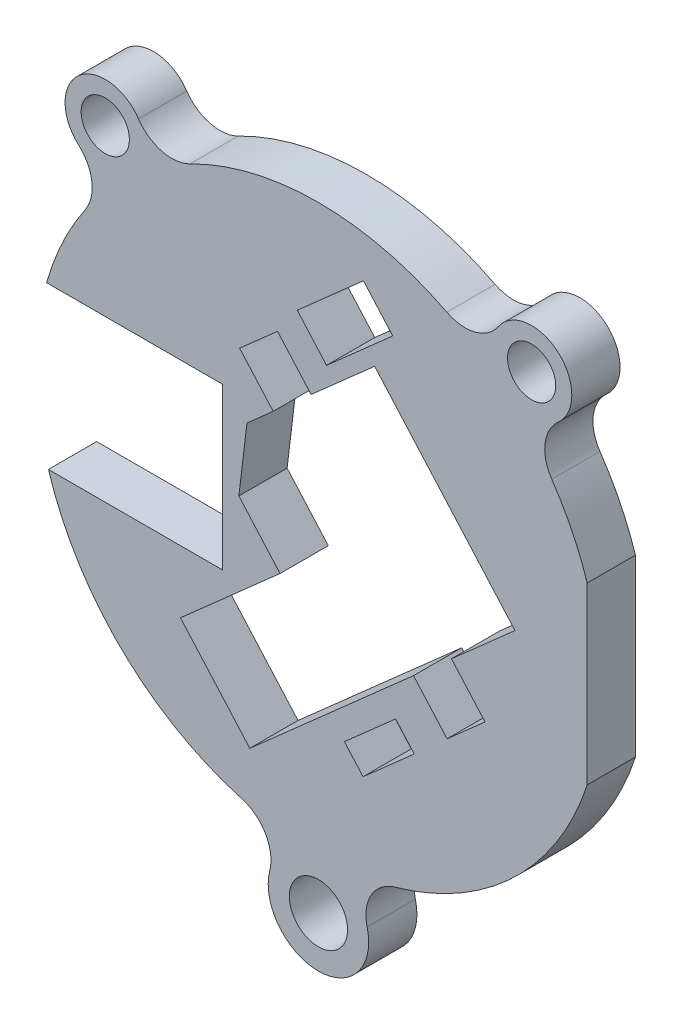
SolidWorks part; units mm, degrees
ref_plane "Front Plane" through (0, 0, 0) normal (0, 0, 1) x (1, 0, 0)
ref_plane "Top Plane" through (0, 0, 0) normal (0, 1, 0) x (1, 0, 0)
ref_plane "Right Plane" through (0, 0, 0) normal (1, 0, 0) x (0, 0, -1)
sketch "Sketch1" plane through (0, 0, 0) normal (0, 0, 1) x (1, 0, 0)
  line L0 (-21.141, 18.2245) -> (20.1141, 18.2245) construction
  line L1 (-4.8006, 1.8415) -> (-4.8006, -3.0861)
  line L2 (-4.8006, -3.0861) -> (-8.9662, -3.0861)
  line L3 (-8.9662, -3.0861) -> (-8.9662, -5.3514)
  line L4 (-8.9662, -5.3514) -> (-6.5786, -5.3514)
  line L5 (-4.9806, 7.3918) -> (-2.5835, 9.5123)
  line L6 (-2.5835, 9.5123) -> (-0.463, 7.1152)
  line L7 (-4.9806, 7.3918) -> (-2.8601, 4.9947)
  line L8 (3.2088, 10.3632) -> (-4.5153, 3.5306)
  line L9 (12.0777, 0.3371) -> (4.3536, -6.4955)
  line L10 (-4.5153, 3.5306) -> (-5.0276, -0.7207)
  line L11 (-5.0276, -0.7207) -> (0.0716, -6.4852)
  line L12 (0.0716, -6.4852) -> (4.3536, -6.4955)
  line L13 (-2.478, -3.6029) -> (7.6432, 5.3502) construction
  line L14 (3.2088, 10.3632) -> (12.0777, 0.3371)
  line L15 (3.2088, 10.3632) -> (11.8761, 18.0302)
  line L16 (-9.2588, -8.622) -> (-4.7522, -4.6355) construction
  line L17 (-9.2588, -8.622) -> (-5.994, -12.3128) construction
  line L18 (-4.7522, -4.6355) -> (-1.4874, -8.3263) construction
  line L19 (-5.994, -12.3128) -> (-1.4874, -8.3263) construction
  line L20 (12.0777, 0.3371) -> (20.228, 7.5468)
  line L21 (-6.5786, -5.3514) -> (-6.5786, -5.8039)
  line L22 (-6.5786, -5.8039) -> (-14.0208, -5.8039)
  line L23 (-14.0208, -5.8039) -> (-14.0208, 4.5593)
  line L24 (-14.0208, 4.5593) -> (-6.5786, 4.5593)
  line L25 (-6.5786, 4.5593) -> (-6.5786, 3.9924)
  line L26 (-6.5786, 3.9924) -> (-8.9662, 3.9924)
  line L27 (-8.9662, 3.9924) -> (-8.9662, 1.8415)
  line L28 (-8.9662, 1.8415) -> (-4.8006, 1.8415)
  line L29 (8.4059, -2.9109) -> (10.5264, -5.308)
  line L30 (10.5264, -5.308) -> (8.1292, -7.4285)
  line L31 (8.1292, -7.4285) -> (6.0088, -5.0313)
  line L32 (-4.7522, -4.6355) -> (-2.9639, -3.0536) construction
  line L33 (-1.4874, -8.3263) -> (0.5926, -6.4864) construction
  line L34 (-5.4555, -12.9216) -> (-0.9489, -8.9351)
  line L35 (-8.7203, -9.2308) -> (-4.2137, -5.2443)
  line L36 (-8.7203, -9.2308) -> (-5.4555, -12.9216)
  line L37 (-0.9489, -8.9351) -> (1.816, -6.4894)
  line L38 (-4.2137, -5.2443) -> (-2.4254, -3.6624)
  arc A0 (-15.2315, -0.5079) -> (3.302, 14.878) centre (0, 0) ccw construction
  circle A1 centre (0, 0) radius 21.59 construction
  circle A2 centre (0, 0) radius 21.59
  circle A3 centre (0, -18.415) radius 1.4224 construction
  circle A4 centre (0, 18.415) radius 1.4224 construction
  circle A5 centre (0, -18.415) radius 1.4224
  circle A6 centre (0, 18.415) radius 1.4224
  circle A7 centre (0, 0) radius 15.24
  dimension "D3" = 30.48
  dimension "D1" = 33.4645
  dimension "D2" = 20.0406
  dimension "D4" = 4.9276
  dimension "D5" = 2.7178
  dimension "D6" = 8.7122
  dimension "D7" = 7.8613
  dimension "D8" = 2.7178
  dimension "D9" = 3.2004
  dimension "D10" = 13.3858
  dimension "D11" = 3.1623
  dimension "D12" = 10.3124
  dimension "D13" = 8.6106
  dimension "D14" = 7.6962
  dimension "D15" = 6.0168
  dimension "D16" = 2.3876
  dimension "D17" = 4.9276
  dimension "D18" = 22.86
  dimension "D19" = 7.4422
  dimension "D20" = 5.0546
  dimension "D21" = 13.6652
  dimension "D22" = 29.2608
  dimension "D23" = 0.8128
extrude "Boss-Extrude1" add sketch "Sketch1" along normal blind 3.048 contours L15 A7 L20 L9 L29 L30 L31 L12 L33 L19 L17 L16 L32 L11 L1 L2 L3 L4 L21 L22 L23 L24 L25 L26 L27 L28 L10 L8 L7 L5 L6 | L28 L27 L26 L25 L24 L23 L22 L21 L4 L3 L2 L1 L11 L10 | A7 L15 A2 L20 A6 A5 region at (-6.8834, 2.2726, 0) region at (-10.1343, -0.6067, 0) region at (-13.5004, -8.3055, 0)
sketch "Sketch2" plane through (0, 0, 3.048) normal (0, 0, 1) x (1, 0, 0)
  line L0 (-5.0276, 2.3876) -> (-5.0276, -2.794)
  line L1 (-5.0276, 2.3876) -> (-10.4871, 2.3876)
  line L2 (-10.4871, 2.3876) -> (-10.4871, 3.8608)
  line L3 (-10.4871, 3.8608) -> (-7.085, 3.8608)
  line L4 (-7.085, 3.8608) -> (-7.085, 4.8768)
  line L5 (-7.085, 4.8768) -> (-14.4764, 4.8768)
  line L6 (-14.4764, 4.8768) -> (-14.4764, -5.2832)
  line L7 (-14.4764, -5.2832) -> (-7.085, -5.2832)
  line L8 (-7.085, -5.2832) -> (-7.085, -4.2672)
  line L9 (-7.085, -4.2672) -> (-10.4871, -4.2672)
  line L10 (-10.4871, -4.2672) -> (-10.4871, -2.794)
  line L11 (-10.4871, -2.794) -> (-5.0276, -2.794)
  line L12 (-5.0276, 2.3876) -> (-4.653, 2.3876)
  line L13 (-4.5153, 3.5306) -> (-5.0276, -0.7207) construction
  line L14 (-5.0276, -2.794) -> (-3.1935, -2.794)
  line L15 (-5.0276, -0.7207) -> (-2.4254, -3.6624) construction
  line L16 (-7.085, 3.8608) -> (-7.085, -4.2672)
  line L17 (-14.4764, 4.8768) -> (-21.032, 4.8768)
  line L18 (-14.4764, -5.2832) -> (-20.9336, -5.2832)
  arc A0 (11.8761, 18.0302) -> (20.228, 7.5468) centre (0, 0) ccw construction
  arc M2 (11.8761, 18.0302) -> (20.228, 7.5468) centre (0, 0) ccw
  dimension "D1" = 9.4488
  dimension "D2" = 7.3914
  dimension "D3" = 10.16
  dimension "D4" = 1.016
  dimension "D5" = 5.1816
  dimension "D6" = 5.4596
  dimension "D7" = 1.4732
  dimension "D8" = 1.143
extrude "Cut-Extrude3" cut sketch "Sketch2" against normal through all contours L10 L11 L0 L1 L2 L3 L4 L5 L6 L7 L8 L9 | L16 L3 L2 L1 | L16 L11 L10 L9 | L18 L6 L17 M2 region at (-11.0879, -0.2032, 3.048) region at (-8.7861, 3.1242, 3.048) region at (-8.7861, -3.5306, 3.048) region at (-17.9346, -0.1913, 3.048)
sketch "Sketch3" plane through (0, 0, 0) normal (0, 0, -1) x (-1, 0, 0)
  line L0 (-20.8712, -5.5245) -> (-16.9841, -5.5245)
  line L1 (-16.9841, -5.5245) -> (-20.8712, -5.5245) construction
  line L2 (-16.9841, -5.5245) -> (-16.9841, 4.6772)
  line L3 (-8.4059, -2.9109) -> (-20.228, 7.5468) construction
  line L4 (-16.9841, 5.5245) -> (-16.9841, -5.5245) construction
  line L5 (-16.9841, 4.6772) -> (-20.228, 7.5468)
  arc A0 (-20.228, 7.5468) -> (20.9336, -5.2832) centre (0, 0) ccw construction
  arc A1 (-20.228, 7.5468) -> (-20.8712, -5.5245) centre (0, 0) ccw
  arc A2 (-20.8712, -5.5245) -> (-20.8712, 5.5245) centre (0, 0) ccw construction
extrude "Cut-Extrude4" cut sketch "Sketch3" against normal through all
sketch "Sketch4" plane through (0, 0, 0) normal (0, 0, -1) x (-1, 0, 0)
  line L0 (-12.3201, -16.1591) -> (12.3201, 16.1591) construction
  line L1 (-13.8351, -15.0041) -> (10.8052, 17.3141)
  line L2 (-10.8052, -17.3141) -> (13.8351, 15.0041)
  line L3 (-16.1591, 12.3201) -> (16.1591, -12.3201) construction
  line L4 (-15.0041, 13.8351) -> (17.3141, -10.8052)
  line L5 (-17.3141, 10.8052) -> (15.0041, -13.8351)
  line L6 (-16.9841, 5.5245) -> (-16.9841, 4.6772)
  line L7 (-16.9841, 4.6772) -> (-12.4201, 0.64)
  line L8 (-8.4059, -2.9109) -> (-16.9841, 4.6772) construction
  line L9 (-12.4201, 0.64) -> (-3.5512, 10.6661)
  line L10 (0.463, 7.1152) -> (-11.8761, 18.0302) construction
  line L11 (-3.5512, 10.6661) -> (-8.9594, 15.4501)
  line L12 (5.0276, -0.7207) -> (2.4254, -3.6624) construction
  line L13 (0, 0) -> (2.7145, -20.1379) construction
  line L14 (1.8879, 0.2545) -> (4.6025, -19.8834)
  line L15 (-1.8879, -0.2545) -> (0.8266, -20.3924)
  line L16 (-16.1591, 12.3201) -> (12.3201, 16.1591) construction
  circle A0 centre (0, 0) radius 17.86
  arc A1 (-13.8351, -15.0041) -> (-10.8052, -17.3141) centre (-12.3201, -16.1591) ccw
  arc A2 (13.8351, 15.0041) -> (10.8052, 17.3141) centre (12.3201, 16.1591) ccw
  arc A3 (-15.0041, 13.8351) -> (-17.3141, 10.8052) centre (-16.1591, 12.3201) ccw
  arc A4 (15.0041, -13.8351) -> (17.3141, -10.8052) centre (16.1591, -12.3201) ccw
  circle A5 centre (12.3201, 16.1591) radius 1.1049
  circle A6 centre (16.1591, -12.3201) radius 1.1049
  circle A7 centre (-12.3201, -16.1591) radius 1.1049
  circle A8 centre (-16.1591, 12.3201) radius 1.1049
  arc A9 (1.8879, 0.2545) -> (-1.8879, -0.2545) centre (0, 0) ccw
  arc A10 (0.8266, -20.3924) -> (4.6025, -19.8834) centre (2.7145, -20.1379) ccw
  arc A11 (2.7145, -20.1379) -> (16.1591, -12.3201) centre (0, 0) ccw construction
  circle A12 centre (2.7145, -20.1379) radius 1.1049
  point P6 (0, 0)
  point P13 (0, 0)
  point P39 (1.3573, -10.0689)
  line M1 (-8.4059, -2.9109) -> (-16.9841, 4.6772)
  line M3 (-16.9841, -5.5245) -> (-20.8712, -5.5245)
  arc M4 (-20.8712, -5.5245) -> (20.9336, -5.2832) centre (0, 0) ccw
  line M5 (20.9336, -5.2832) -> (7.085, -5.2832)
  line M7 (7.085, 4.8768) -> (21.032, 4.8768)
  arc M8 (21.032, 4.8768) -> (-11.8761, 18.0302) centre (0, 0) ccw
  line M9 (-11.8761, 18.0302) -> (0.463, 7.1152)
  circle M24 centre (0, 18.415) radius 1.4224
  circle M25 centre (0, -18.415) radius 1.4224
  dimension "D1" = 3.81
  dimension "D2" = 3.81
  dimension "D3" = 13.97
extrude "Boss-Extrude2" add sketch "Sketch4" against normal up to vertex (3.048 mm away) contours A0 L4 L9 M9 | L4 A0 L5 L9 | L5 A0 L6 L9 M1 | L4 A3 L5 A0 A8 | A2 L1 A0 L2 A5 M8 | A0 M24 | A0 M25 | A0 L15 M25 | L15 A0 M25 | A10 M4 | A2 M8 region at (13.4131, 4.8762, 0) region at (10.9588, 8.3691, 0) region at (16.2523, 10.0852, 0) region at (0.2829, -17.4804, 0) region at (-2.9174, -21.6425, 0) region at (8.1323, 11.4955, 0) region at (-0.7535, -17.5272, 0) region at (-0.9598, -18.5708, 0) region at (-10.0849, 16.2525, 0) region at (0, 17.4932, 0) region at (-13.2407, 17.3665, 0) up to point (10.5264, -5.308, 3.048)
extrude "Cut-Extrude5" cut sketch "Sketch4<3>" against normal through all contours A4 L5 A0 L2 A1 M25 M4 | A4 A0 L4 M4 M5 | A1 L1 A0 M3 M4 | A7 | A6 | A5 | A2 L2 A0 M7 M8 | A2 A0 L1 M8 M9 M24 | L1 A1 L2 A0 A7 M4 | A10 A4 L5 A0 L14 M4 | A4 L4 A0 L5 A6 M4 | A12 region at (16.6582, -10.306, 0) region at (13.002, -14.0284, 0) region at (5.4053, -18.8788, 0) region at (-9.8123, -16.8747, 0) region at (-5.4955, 17.2518, 0) region at (-15.6105, -14.0703, 0) region at (-16.798, 10.0037, 0) region at (-18.1332, -7.9591, 0) region at (-12.3201, 16.1591, 0) region at (-16.1591, -12.3201, 0) region at (12.3201, -16.1591, 0) region at (-2.7145, -20.1379, 0)
sketch "Sketch4<3>" plane through (0, 0, 0) normal (0, 0, -1) x (-1, 0, 0) same geometry as "Sketch4"
sketch "Sketch5" plane through (0, 0, 3.048) normal (0, 0, 1) x (1, 0, 0)
  line L0 (4.3536, -6.4955) -> (-4.3384, -14.1843)
  line L1 (-4.3384, -14.1843) -> (-5.4555, -12.9216)
  line L2 (-8.7203, -9.2308) -> (-5.4555, -12.9216) construction
  line L3 (6.0088, -5.0313) -> (4.3536, -6.4955) construction
  line L4 (-5.4555, -12.9216) -> (1.816, -6.4894)
  line L5 (1.816, -6.4894) -> (4.3536, -6.4955)
extrude "Cut-Extrude10" cut sketch "Sketch5" against normal through all
sketch "Sketch6" plane through (0, 0, 3.048) normal (0, 0, 1) x (1, 0, 0)
  line L0 (17.3141, 10.8052) -> (15.2768, 9.2519) construction
  line L1 (15.0041, 13.8351) -> (12.9668, 12.2818) construction
  line L2 (17.3141, 10.8052) -> (15.2768, 9.2519)
  line L3 (15.0041, 13.8351) -> (12.9668, 12.2818)
  line L4 (17.5451, 10.5023) -> (15.472, 8.9216)
  line L5 (14.7731, 14.138) -> (12.7, 12.5574)
  line L23 (-4.9801, -19.8325) -> (-4.6378, -17.2935)
  line L24 (-0.1068, -17.9043) -> (-0.449, -20.4433)
  line L25 (-4.9801, -19.8325) -> (-4.6318, -17.2489)
  line L26 (-0.1008, -17.8597) -> (-0.449, -20.4433)
  line L29 (14.7731, 14.138) -> (12.7358, 12.5847) construction
  line L30 (17.5451, 10.5023) -> (15.5078, 8.9489) construction
  line L31 (-14.138, 14.7731) -> (-12.5847, 12.7358)
  line L32 (-8.9489, 15.5078) -> (-10.5023, 17.5451)
  line L33 (-14.138, 14.7731) -> (-12.5574, 12.7)
  line L34 (-8.9216, 15.472) -> (-10.5023, 17.5451)
  arc A0 (17.3141, 10.8052) -> (15.0041, 13.8351) centre (16.1591, 12.3201) ccw construction
  arc A1 (17.3141, 10.8052) -> (15.0041, 13.8351) centre (16.1591, 12.3201) ccw
  arc A2 (17.5451, 10.5023) -> (14.7731, 14.138) centre (16.1591, 12.3201) ccw
  arc A11 (-4.9801, -19.8325) -> (-0.449, -20.4433) centre (-2.7145, -20.1379) ccw
  arc A12 (-4.9801, -19.8325) -> (-0.449, -20.4433) centre (-2.7145, -20.1379) ccw
  circle A14 centre (0, 0) radius 17.86
  arc A15 (-10.5023, 17.5451) -> (-14.138, 14.7731) centre (-12.3201, 16.1591) ccw
  arc A16 (-10.5023, 17.5451) -> (-14.138, 14.7731) centre (-12.3201, 16.1591) ccw
  line M25 (-4.2602, -17.3444) -> (-4.6025, -19.8834)
  arc M26 (-4.6025, -19.8834) -> (-0.8266, -20.3924) centre (-2.7145, -20.1379) ccw
  line M27 (-0.8266, -20.3924) -> (-0.4844, -17.8534)
  arc M28 (-0.4844, -17.8534) -> (16.9841, -5.5245) centre (0, 0) ccw
  arc M30 (16.9841, 5.5245) -> (15.2768, 9.2519) centre (0, 0) ccw
  line M31 (15.2768, 9.2519) -> (17.3141, 10.8052)
  arc M32 (17.3141, 10.8052) -> (15.0041, 13.8351) centre (16.1591, 12.3201) ccw
  line M33 (15.0041, 13.8351) -> (12.9668, 12.2818)
  arc M34 (12.9668, 12.2818) -> (-9.2519, 15.2768) centre (0, 0) ccw
  line M35 (-9.2519, 15.2768) -> (-10.8052, 17.3141)
  arc M36 (-10.8052, 17.3141) -> (-13.8351, 15.0041) centre (-12.3201, 16.1591) ccw
  line M37 (-13.8351, 15.0041) -> (-12.2818, 12.9668)
  arc M38 (-12.2818, 12.9668) -> (-17.1812, 4.8768) centre (0, 0) ccw
  arc M42 (-17.0607, -5.2832) -> (-4.2602, -17.3444) centre (0, 0) ccw
  dimension "D1" = 0.381
  dimension "D2" = 0.381
  dimension "D3" = 0.381
extrude "Boss-Extrude3" add sketch "Sketch6" against normal up to vertex contours L34 A16 L33 M38 M37 M36 M35 M34 | L25 A12 L26 M28 M27 M26 M25 M42 | L4 A2 L5 M34 M33 M32 M31 M30 region at (17.7383, 13.5242, 3.048) region at (-9.1284, 15.4449, 3.048) region at (-0.1744, -17.8725, 3.048) up to point (8.4059, -2.9109, 0)
sketch "Sketch7" plane through (0, 0, 0) normal (0, 0, -1) x (-1, 0, 0)
  line L0 (7.085, 4.8768) -> (6.0563, 4.8768)
  line L1 (6.0563, 4.8768) -> (6.0563, -5.2832)
  line L2 (6.0563, -5.2832) -> (7.085, -5.2832)
  line L3 (5.0276, -0.7207) -> (7.085, -0.7207) construction
  line L4 (7.085, 4.8768) -> (7.085, -5.2832) construction
  line L5 (7.085, 4.8768) -> (7.085, -5.2832)
  point P11 (6.0563, -0.7207)
extrude "Cut-Extrude11" cut sketch "Sketch7" against normal through all
sketch "Sketch8" plane through (0, 0, 3.048) normal (0, 0, 1) x (1, 0, 0)
  circle A0 centre (0, 0) radius 17.86
  circle A1 centre (0, 0) radius 23.4976
extrude "Cut-Extrude12" cut sketch "Sketch8" against normal through all
sketch "Sketch9" plane through (0, 0, 3.048) normal (0, 0, 1) x (1, 0, 0)
  line L0 (0, 17.86) -> (-14.5094, 17.86) construction
  circle A0 centre (13.4706, 15.32) radius 1.524
  circle A1 centre (13.4706, 15.32) radius 2.54
  circle A2 centre (16.8382, 11.5166) radius 2.54
  circle A3 centre (9.2677, 18.1733) radius 2.54
  circle A4 centre (-13.4706, 15.32) radius 2.54
  circle A5 centre (-9.2677, 18.1733) radius 2.54
  circle A6 centre (-16.8382, 11.5166) radius 2.54
  circle A7 centre (0, -21.035) radius 1.8415
  circle A8 centre (0, -21.035) radius 3.175
  circle A9 centre (5.5404, -19.6332) radius 2.54
  circle A10 centre (-5.5404, -19.6332) radius 2.54
  circle A11 centre (-13.4706, 15.32) radius 1.524
  circle A12 centre (0, 0) radius 17.86
  circle A13 centre (0, 0) radius 17.86
  arc A14 (16.9841, 5.5245) -> (-17.1812, 4.8768) centre (0, 0) ccw construction
  arc M17 (16.9841, 5.5245) -> (-17.1812, 4.8768) centre (0, 0) ccw
  arc M21 (-17.0607, -5.2832) -> (16.9841, -5.5245) centre (0, 0) ccw
  dimension "D1" = 3.048
  dimension "D2" = 5.08
  dimension "D3" = 5.08
  dimension "D4" = 5.08
  dimension "D5" = 3.683
  dimension "D6" = 6.35
  dimension "D7" = 5.08
extrude "Boss-Extrude4" add sketch "Sketch9" against normal up to vertex contours A2 A1 M17 | A1 A0 | A3 A1 M17 | A6 A4 M17 | A4 A11 | A5 A4 M17 | A8 A7 | A10 A8 M21 | A9 A8 M21 region at (15.7212, 14.3067, 3.048) region at (10.3242, 15.2074, 3.048) region at (13.7616, 12.185, 3.048) region at (-10.3242, 15.2074, 3.048) region at (-11.1114, 16.0451, 3.048) region at (-13.7616, 12.185, 3.048) region at (2.6103, -18.2487, 3.048) region at (3.0615, -20.6537, 3.048) region at (-2.6103, -18.2487, 3.048) up to point (-0.463, 7.1152, 0)
sketch "Sketch10" plane through (0, 0, 3.048) normal (0, 0, 1) x (1, 0, 0)
  circle A0 centre (-10.8325, -7.6454) radius 1.143
  circle A1 centre (0, -13.2588) radius 1.143
  circle A2 centre (8.579, 10.1092) radius 1.143
  dimension "D1" = 2.286
extrude "Cut-Extrude13" [suppressed] cut sketch "Sketch10" against normal through all
sketch "Sketch11" plane through (0, 0, 3.048) normal (0, 0, 1) x (1, 0, 0)
  line L0 (-1.341, 11.2896) -> (0.5102, 9.1969)
  line L1 (0.5102, 9.1969) -> (4.6956, 12.8993)
  line L2 (4.6956, 12.8993) -> (2.8445, 14.992)
  line L3 (2.8445, 14.992) -> (-1.341, 11.2896)
  line L5 (-2.5835, 9.5123) -> (-0.463, 7.1152) construction
  line L6 (6.0533, -9.2987) -> (2.8191, -12.1596)
  line L7 (2.8191, -12.1596) -> (1.6411, -10.8279)
  line L8 (1.6411, -10.8279) -> (4.8753, -7.967)
  line L9 (4.8753, -7.967) -> (6.0533, -9.2987)
  line L10 (-4.9806, 7.3918) -> (-2.5835, 9.5123) construction
  line L11 (8.1292, -7.4285) -> (6.0088, -5.0313) construction
  line L12 (10.5264, -5.308) -> (8.1292, -7.4285) construction
  point P6 (-1.5232, 8.3137)
  dimension "D1" = 2.794
  dimension "D2" = 2.1082
  dimension "D3" = 5.588
  dimension "D4" = 1.778
  dimension "D5" = 4.318
  dimension "D6" = 2.794
  dimension "D7" = 0.0254
  dimension "D8" = 0.508
extrude "Cut-Extrude14" cut sketch "Sketch11" against normal through all
sketch "Sketch13" plane through (0, 0, 3.048) normal (0, 0, 1) x (1, 0, 0)
  line B0 (-6.0563, 4.8768) -> (-17.1812, 4.8768)
  line B1 (-6.0563, 4.8768) -> (-6.0563, -5.2832)
  line B2 (-17.0607, -5.2832) -> (-6.0563, -5.2832)
  line B3 (-8.7203, -9.2308) -> (-2.4254, -3.6624)
  line B4 (-8.7203, -9.2308) -> (-4.3384, -14.1843)
  line B5 (6.0088, -5.0313) -> (-4.3384, -14.1843)
  line B6 (1.6411, -10.8279) -> (2.8023, -12.1406)
  line B7 (4.8753, -7.967) -> (1.6411, -10.8279)
  line B8 (2.8023, -12.1406) -> (6.0365, -9.2797)
  line B9 (6.0365, -9.2797) -> (4.8753, -7.967)
  line B10 (8.1292, -7.4285) -> (6.0088, -5.0313)
  line B11 (10.5264, -5.308) -> (8.1292, -7.4285)
  line B12 (8.4059, -2.9109) -> (10.5264, -5.308)
  line B13 (8.4059, -2.9109) -> (12.4201, 0.64)
  line B14 (12.4201, 0.64) -> (3.5512, 10.6661)
  line B15 (-0.463, 7.1152) -> (3.5512, 10.6661)
  line B16 (-2.5835, 9.5123) -> (-0.463, 7.1152)
  line B17 (-4.9806, 7.3918) -> (-2.5835, 9.5123)
  line B18 (-4.9806, 7.3918) -> (-2.8601, 4.9947)
  line B19 (-2.8601, 4.9947) -> (-4.5153, 3.5306)
  line B20 (-4.5153, 3.5306) -> (-5.0276, -0.7207)
  line B21 (-5.0276, -0.7207) -> (-2.4254, -3.6624)
  line B22 (-1.0044, 10.9091) -> (0.8468, 8.8164)
  line B23 (3.181, 14.6115) -> (-1.0044, 10.9091)
  line B24 (5.0322, 12.5188) -> (3.181, 14.6115)
  line B25 (0.8468, 8.8164) -> (5.0322, 12.5188)
  line B26 (16.9841, -5.5245) -> (16.9841, 5.5245)
  circle B27 centre (-10.8325, -7.6454) radius 1.143
  circle B28 centre (0, -13.2588) radius 1.143
  circle B29 centre (8.579, 10.1092) radius 1.143
sketch_block_instance "Block1-1"
sketch_block "Block1"
